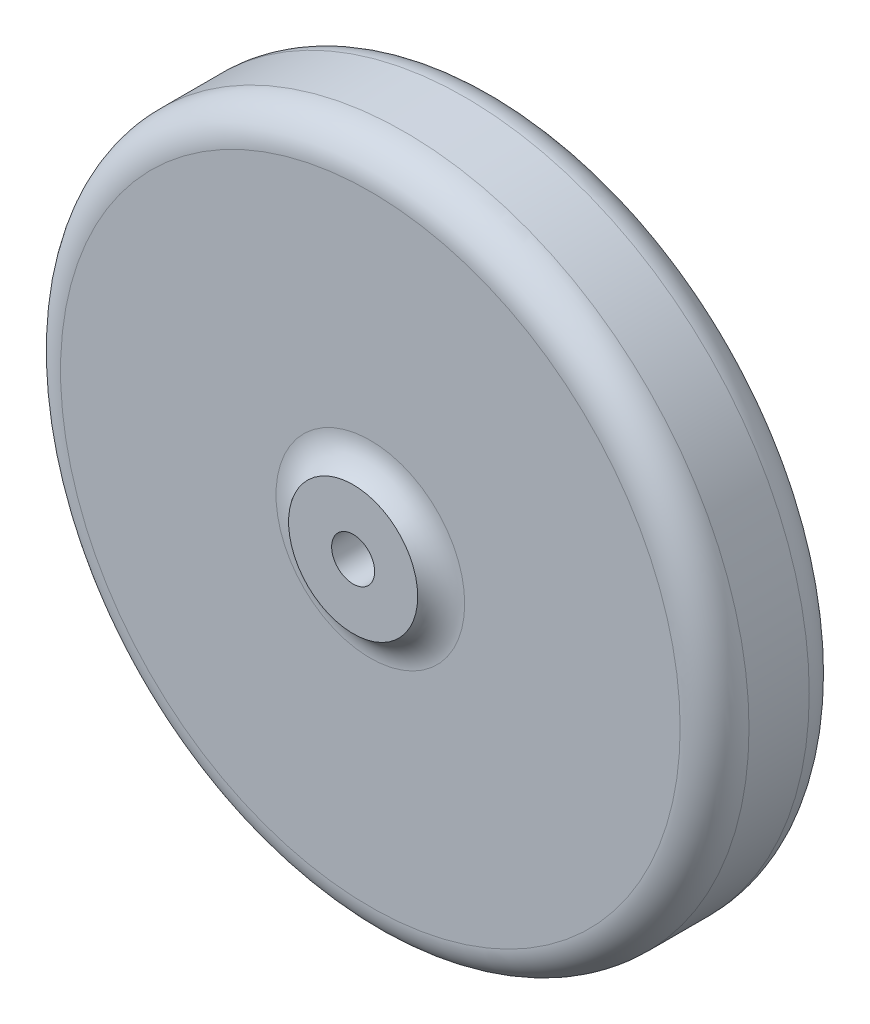
SolidWorks part; units mm, degrees
material "Rubber"
ref_plane "Front Plane" through (0, 0, 0) normal (0, 0, 1) x (1, 0, 0)
ref_plane "Top Plane" through (0, 0, 0) normal (0, 1, 0) x (1, 0, 0)
ref_plane "Right Plane" through (0, 0, 0) normal (1, 0, 0) x (0, 0, -1)
sketch "Sketch1" plane through (0, 0, 0) normal (0, 0, 1) x (1, 0, 0)
  circle A0 centre (0, 0) radius 63.5
extrude "Boss-Extrude1" add sketch "Sketch1" along normal mid plane 23.8125
sketch "Sketch2" plane through (0, 0, 0) normal (0, 0, 1) x (1, 0, 0)
  circle A0 centre (0, 0) radius 11.9062
extrude "Boss-Extrude2" add sketch "Sketch2" along normal mid plane 30.1625
sketch "Sketch3" plane through (0, 0, 0) normal (0, 0, 1) x (1, 0, 0)
  circle A0 centre (0, 0) radius 3.9688
extrude "Cut-Extrude1" cut sketch "Sketch3" against normal through all both and the other way through all
fillet "Fillet1" radius 6.35 4 edges at (11.9062, 0, -11.9062) (63.5, 0, -11.9062) (63.5, 0, 11.9062) (11.9062, 0, 11.9062)
